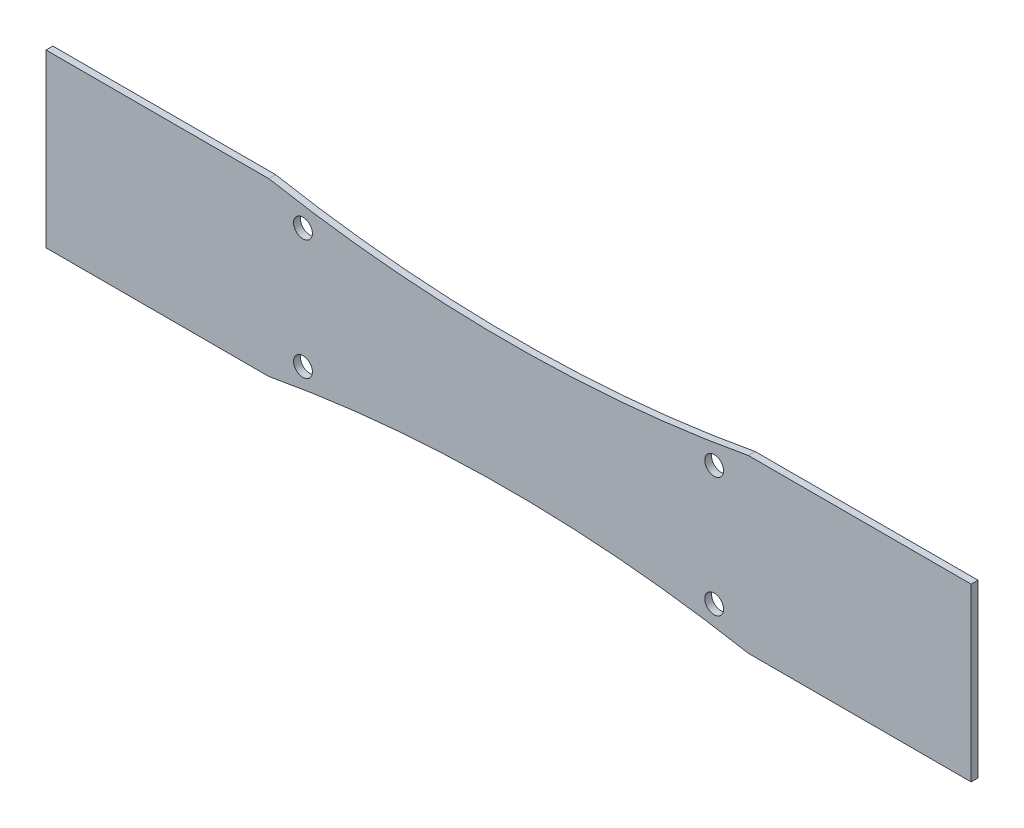
SolidWorks part; units mm, degrees
material "1023 Carbon Steel Sheet (SS)"
ref_plane "Front Plane" through (0, 0, 0) normal (0, 0, 1) x (1, 0, 0)
ref_plane "Top Plane" through (0, 0, 0) normal (0, 1, 0) x (1, 0, 0)
ref_plane "Right Plane" through (0, 0, 0) normal (1, 0, 0) x (0, 0, -1)
sketch "Sketch1" plane through (0, 0, 0) normal (0, 0, 1) x (1, 0, 0)
  line L0 (70, 25) -> (70, -25) construction
  line L1 (135, -25) -> (70, -25)
  line L2 (135, -25) -> (135, 25)
  line L3 (135, 25) -> (70, 25)
  line L4 (-135, -25) -> (-135, 25)
  line L5 (135, -25) -> (-135, 25) construction
  line L6 (135, 25) -> (-135, -25) construction
  line L7 (-70, 0) -> (70, 0) construction
  line L8 (-70, 25) -> (-70, -25) construction
  line L9 (-70, 25) -> (-135, 25)
  line L10 (-70, -25) -> (-135, -25)
  arc A0 (-70, 25) -> (70, 25) centre (0, 403.9202) ccw
  arc A1 (-70, -25) -> (70, -25) centre (0, -403.9202) cw
  point P0 (0, 0)
  dimension "D1" = 50
  dimension "D3" = 65
  dimension "D4" = 65
extrude "Boss-Extrude1" add sketch "Sketch1" along normal blind 2
sketch "Sketch2" plane through (0, 0, 2) normal (0, 0, 1) x (1, 0, 0)
  line L0 (-135, 0) -> (135, 0) construction
  line L1 (-135, 25) -> (-135, -25) construction
  line L2 (135, -25) -> (135, 25) construction
  line L3 (-60, -17.5) -> (-60, 17.5)
  line L4 (0, 0) -> (0, 12.0359) construction
  line L5 (60, -17.5) -> (60, 17.5)
  point P9 (-60, 0)
  dimension "D1" = 35
  dimension "D2" = 60
hole_wizard "M5 Clearance Hole1" positions "3DSketch1" profile "Sketch3" hole size "M5" standard "ISO" end condition through all
sketch3d "3DSketch1"
  point P0 (-60, 17.5, 2)
  point P3 (-60, -17.5, 2)
  point P6 (60, 17.5, 2)
  point P9 (60, -17.5, 2)
sketch "Sketch3" plane through (-60, 17.5, 2) normal (1, 0, 0) x (0, -1, 0)
  line L0 (0, 0) -> (0, 2)
  line L1 (0, 2) -> (2.75, 2)
  line L2 (2.75, 2) -> (2.75, 0)
  line L5 (2.75, 0) -> (0, 0)
  line L11 (0, -6.35) -> (0, 107.95) construction
  dimension "Thru Hole Dia." = 5.5
  dimension "Thru Hole Depth" = 2
